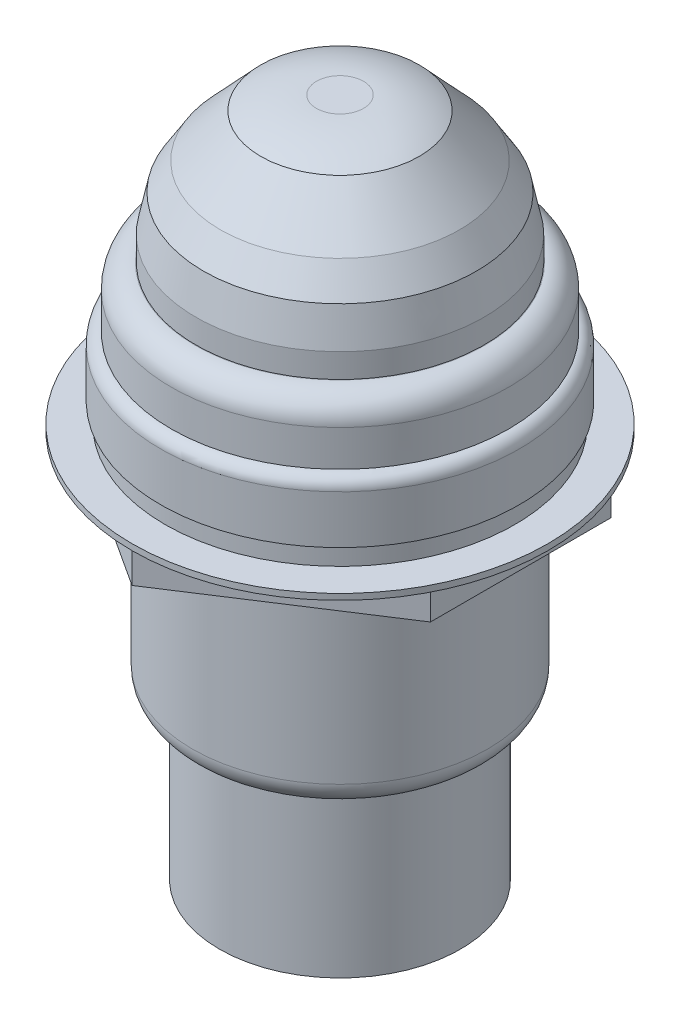
SolidWorks part; units mm, degrees
ref_plane "Front Plane" through (0, 0, 0) normal (0, 0, 1) x (1, 0, 0)
ref_plane "Top Plane" through (0, 0, 0) normal (0, 1, 0) x (1, 0, 0)
ref_plane "Right Plane" through (0, 0, 0) normal (1, 0, 0) x (0, 0, -1)
sketch "Sketch1" plane through (0, 0, 0) normal (0, 1, 0) x (1, 0, 0)
  circle A0 centre (0, 0) radius 12.1412
  dimension "D1" = 24.2824
extrude "Boss-Extrude1" add sketch "Sketch1" along normal blind 12.192
fillet "Fillet1" radius 10.16 1 edges at (0, 12.192, 12.1412)
sketch "Sketch3" plane through (0, 0, 0) normal (0, -1, 0) x (1, 0, 0)
  circle A0 centre (0, 0) radius 14.224
  dimension "D1" = 28.448
extrude "Boss-Extrude2" add sketch "Sketch3" along normal blind 5.08
sketch "Sketch4" plane through (0, 0, 0) normal (1, 0, 0) x (0, 0, -1)
  line L0 (0, 0) -> (0, 12.192) construction
  line L1 (1.9812, 12.192) -> (-1.9812, 12.192) construction
  line L2 (0, 6.096) -> (11.293, 6.096) construction
  line L3 (11.293, 6.096) -> (6.6815, 11.0394)
  line L4 (6.6815, 11.0394) -> (11.293, 11.0394)
  line L5 (11.293, 11.0394) -> (11.293, 6.096)
  arc A0 (12.1412, 2.032) -> (1.9812, 12.192) centre (1.9812, 2.032) ccw construction
  dimension "D1" = 6.6815
revolve "Cut-Revolve1" cut sketch "Sketch4" angle 360 about L0
sketch "Sketch5" plane through (0, 0, 0) normal (1, 0, 0) x (0, 0, -1)
  line L0 (0, 0) -> (0, 6.096) construction
  line L1 (11.293, 6.096) -> (-11.293, 6.096) construction
  line L2 (0, 6.096) -> (11.293, 6.096) construction
  line L3 (12.1412, 2.032) -> (11.293, 6.096)
  line L4 (11.293, 6.096) -> (14.9611, 2.032)
  line L5 (14.9611, 2.032) -> (12.1412, 2.032)
  dimension "D1" = 14.9611
revolve "Cut-Revolve2" cut sketch "Sketch5" angle 360 about L0
sketch "Sketch7" plane through (0, 0, 0) normal (0, 0, 1) x (1, 0, 0)
  line L0 (0, 0) -> (0, 6.096) construction
  line L1 (11.293, 6.096) -> (-11.293, 6.096) construction
  line L2 (0, 6.096) -> (-10.0865, 6.096) construction
  line L3 (-10.0865, 6.096) -> (-10.0865, 7.3893) construction
  line L4 (-6.6815, 11.0394) -> (-11.293, 6.096) construction
  line L5 (-10.0865, 7.3893) -> (-11.8572, 4.5046)
  line L6 (-11.8572, 4.5046) -> (-11.8572, 7.3893)
  line L7 (-11.8572, 7.3893) -> (-10.0865, 7.3893)
  dimension "D1" = 10.0865
  dimension "D2" = 11.8572
  dimension "D3" = 4.5046
revolve "Cut-Revolve3" cut sketch "Sketch7" angle 360 about L0
fillet "Fillet6" radius 2.032 1 edges at (0, 0, -14.224)
sketch "Sketch8" plane through (0, -5.08, 0) normal (0, -1, 0) x (1, 0, 0)
  circle A0 centre (0, 0) radius 15.1213
  dimension "D1" = 30.2425
extrude "Boss-Extrude3" add sketch "Sketch8" along normal blind 5.08
fillet "Fillet7" radius 1.016 1 edges at (0, -5.08, -15.1213)
ref_plane "Plane2" through (-15.24, 0, 0) normal (1, 0, 0) x (0, 0, -1)
sketch "Sketch9" plane through (-15.24, 0, 0) normal (1, 0, 0) x (0, 0, -1)
  line L0 (0, 0) -> (0, -10.0398) construction
  line L1 (-0.127, -10.16) -> (-0.127, -6.089)
  line L2 (-15.1213, -10.16) -> (15.1213, -10.16) construction
  line L3 (-15.1213, -6.089) -> (15.1213, -6.089) construction
  line L4 (-0.127, -6.089) -> (0, -6.089)
  line L5 (0, -6.089) -> (0, -10.16)
  line L6 (0, -10.16) -> (-0.127, -10.16)
  dimension "D1" = 0.127
extrude "Cut-Extrude1" cut sketch "Sketch9" along normal blind 0.254
sketch "Sketch13" plane through (0, -10.16, 0) normal (0, -1, 0) x (1, 0, 0)
  circle A0 centre (0, 0) radius 14.7403
  dimension "D1" = 29.4805
extrude "Boss-Extrude4" add sketch "Sketch13" along normal blind 1.6383
sketch "Sketch14" plane through (0, -11.7983, 0) normal (0, -1, 0) x (1, 0, 0)
  circle A0 centre (0, 0) radius 17.526
  dimension "D1" = 35.052
extrude "Boss-Extrude5" add sketch "Sketch14" along normal blind 0.508
sketch "Sketch15" plane through (0, -12.3063, 0) normal (0, -1, 0) x (1, 0, 0)
  line L0 (0, 0) -> (15.24, 0) construction
  line L1 (15.24, 0) -> (15.24, 7.62) construction
  line L2 (15.24, 7.62) -> (15.24, -7.598)
  line L3 (0, 0) -> (0, 17.526) construction
  line L4 (15.24, 7.62) -> (0, 17.526)
  line L5 (0, 0) -> (0, -17.526) construction
  line L6 (15.24, -7.598) -> (0, -17.526)
  line L7 (-15.24, -7.598) -> (0, -17.526)
  line L8 (-15.24, 7.62) -> (-15.24, -7.598)
  line L9 (-15.24, 7.62) -> (0, 17.526)
  circle A0 centre (0, 0) radius 17.526 construction
  dimension "D1" = 15.24
  dimension "D2" = 7.62
  dimension "D3" = 7.598
extrude "Boss-Extrude6" add sketch "Sketch15" along normal blind 2.54
sketch "Sketch16" plane through (0, -14.8463, 0) normal (0, -1, 0) x (1, 0, 0)
  circle A0 centre (0, 0) radius 12.446
  dimension "D1" = 24.892
extrude "Boss-Extrude7" add sketch "Sketch16" along normal blind 16.51
sketch "Sketch17" plane through (0, -31.3563, 0) normal (0, -1, 0) x (1, 0, 0)
  circle A0 centre (0, 0) radius 10.16
  dimension "D1" = 20.32
extrude "Boss-Extrude8" add sketch "Sketch17" along normal blind 13.716
fillet "Fillet8" radius 2.032 1 edges at (0, -31.3563, -12.446)
